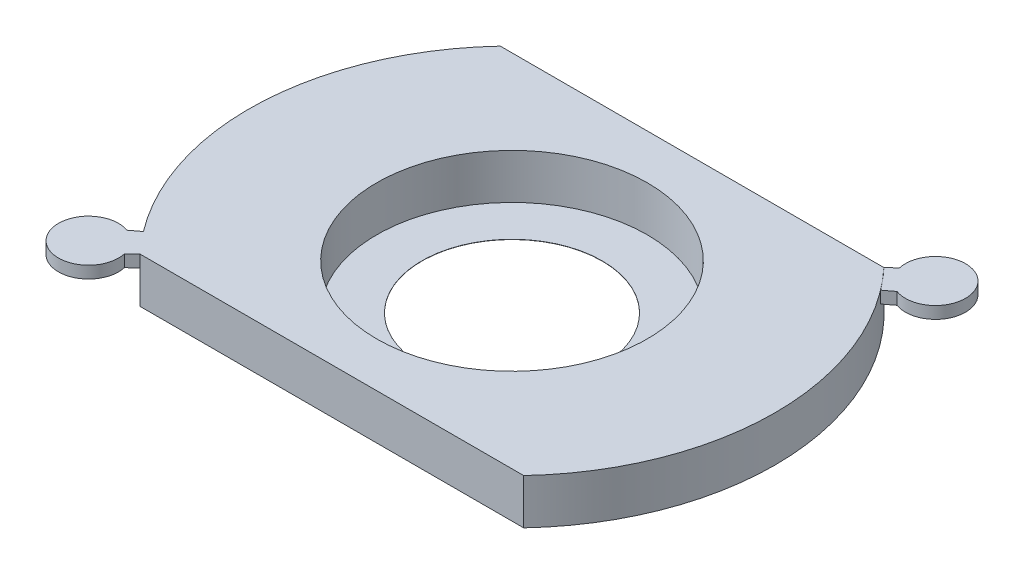
SolidWorks part; units mm, degrees
material "1345 Alloy"
ref_plane "Front Plane" through (0, 0, 0) normal (0, 0, 1) x (1, 0, 0)
ref_plane "Top Plane" through (0, 0, 0) normal (0, 1, 0) x (1, 0, 0)
ref_plane "Right Plane" through (0, 0, 0) normal (1, 0, 0) x (0, 0, -1)
sketch "Sketch1" plane through (0, 0, 0) normal (0, 1, 0) x (1, 0, 0)
  line L0 (-1712.4333, 578.2677) -> (-1658.0172, 559.892) construction
  line L1 (-1682.6566, 611.2885) -> (-1644.8226, 597.5438) construction
  line L2 (-1769.951, 660.0706) -> (-1712.4333, 741.8735) construction
  circle A0 centre (0, 0) radius 1750
  arc A3 (-1712.4333, 578.2677) -> (-1712.4333, 741.8735) centre (-1769.951, 660.0706) cw construction
  arc A4 (-1712.4333, 741.8735) -> (-1682.6566, 611.2885) centre (-1769.951, 660.0706) cw construction
extrude "Boss-Extrude1" add sketch "Sketch1" along normal blind 500
sketch "Sketch2" plane through (0, 500, 0) normal (0, 1, 0) x (1, 0, 0)
  circle A0 centre (0, 0) radius 900
extrude "Cut-Extrude2" cut sketch "Sketch2" against normal blind 300
sketch "Sketch9" plane through (0, 0, 0) normal (0, -1, 0) x (1, 0, 0)
  line L1 (-2106.3119, -1198.0599) -> (2106.3119, -1198.0599)
  line L2 (-2106.3119, -1198.0599) -> (-2106.3119, 1198.0599)
  line L3 (-2106.3119, 1198.0599) -> (2106.3119, 1198.0599)
  line L4 (2106.3119, -1198.0599) -> (2106.3119, 1198.0599)
  line L5 (-2106.3119, -1198.0599) -> (2106.3119, 1198.0599) construction
  line L6 (-2106.3119, 1198.0599) -> (2106.3119, -1198.0599) construction
  line L7 (-2636.6179, -2082.9122) -> (2636.6179, -2082.9122)
  line L8 (-2636.6179, -2082.9122) -> (-2636.6179, 2082.9122)
  line L9 (-2636.6179, 2082.9122) -> (2636.6179, 2082.9122)
  line L10 (2636.6179, -2082.9122) -> (2636.6179, 2082.9122)
  line L11 (-2636.6179, -2082.9122) -> (2636.6179, 2082.9122) construction
  line L12 (-2636.6179, 2082.9122) -> (2636.6179, -2082.9122) construction
  point P0 (0, 0)
  point P6 (0, 0)
extrude "Cut-Extrude10" cut sketch "Sketch9" against normal through all both and the other way through all
sketch "Sketch3" plane through (0, 0, 0) normal (0, -1, 0) x (1, 0, 0)
  circle A0 centre (0, 0) radius 600
extrude "Cut-Extrude3" cut sketch "Sketch3" against normal blind 300
shell "Shell1" thickness 1.5 removed face at (0, 0, -600)
sketch "Sketch10" plane through (0, 198.5, 0) normal (0, -1, 0) x (1, 0, 0)
  line L1 (2226.5426, -1551.0392) -> (-2226.5426, -1551.0392)
  line L2 (2226.5426, -1551.0392) -> (2226.5426, 1551.0392)
  line L3 (2226.5426, 1551.0392) -> (-2226.5426, 1551.0392)
  line L4 (-2226.5426, -1551.0392) -> (-2226.5426, 1551.0392)
  line L5 (2226.5426, -1551.0392) -> (-2226.5426, 1551.0392) construction
  line L6 (2226.5426, 1551.0392) -> (-2226.5426, -1551.0392) construction
  point P0 (0, 0)
extrude "Cut-Extrude11" cut sketch "Sketch10" along normal through all
sketch "Sketch12" plane through (0, 500, 0) normal (0, 1, 0) x (1, 0, 0)
  line L0 (-1275.7204, -1197.9305) -> (-1329.4274, -1248.3625)
  line L1 (-1275.7204, -1197.9305) -> (-1329.4274, -1248.3625)
  line L2 (-1456.8867, -1104.0663) -> (-1394.7434, -1056.9725)
  line L3 (-1212.6439, -1163.1539) -> (-1394.7434, -1056.9725) construction
  line L4 (-1329.4274, -1248.3625) -> (-1275.8583, -1198.0599) construction
  line L5 (1275.5989, -1198.0599) -> (-1275.5989, -1198.0599) construction
  line L6 (-1275.5989, 1198.0599) -> (1275.5989, -1198.0599) construction
  line L7 (0, 0) -> (-1750, 0) construction
  line L13 (0, 0) -> (0, 1750) construction
  line L14 (1212.6439, 1163.1539) -> (1394.7434, 1056.9725) construction
  line L15 (1329.4274, 1248.3625) -> (1275.8583, 1198.0599) construction
  line L16 (1275.7204, 1197.9305) -> (1329.4274, 1248.3625)
  line L17 (1275.7204, 1197.9305) -> (1329.4274, 1248.3625)
  line L18 (1456.8867, 1104.0663) -> (1394.7434, 1056.9725)
  arc A0 (-1275.5989, -1198.0599) -> (-1524.5473, -859.2179) centre (0, 0) cw
  arc A1 (-1275.7204, 1197.9305) -> (-1275.5989, 1198.0599) centre (0, 0) ccw construction
  arc A2 (-1329.4274, -1248.3625) -> (-1456.8867, -1104.0663) centre (-1524.5473, -1292.2737) cw
  arc A3 (-1275.7204, -1197.9305) -> (-1275.5989, -1198.0599) centre (0, 0) cw construction
  arc A4 (1275.8583, 1198.0599) -> (1394.7434, 1056.9725) centre (24.3381, 22.854) cw
  arc A6 (1329.4274, 1248.3625) -> (1456.8867, 1104.0663) centre (1524.5473, 1292.2737) cw
  arc M6 (-1275.5989, 1198.0599) -> (-1275.5989, -1198.0599) centre (0, 0) ccw
extrude "Boss-Extrude2" add sketch "Sketch12" against normal blind 80 contours A2 L0 L2 M6 region at (-1511.5348, 500, 1280.7775)
extrude "Boss-Extrude3" add sketch "Sketch12<6>" against normal blind 80 separate body contours A6 L17 A4 L18 region at (1511.5672, 500, -1280.8004)
sketch "Sketch12<6>" plane through (0, 500, 0) normal (0, 1, 0) x (1, 0, 0) same geometry as "Sketch12"
